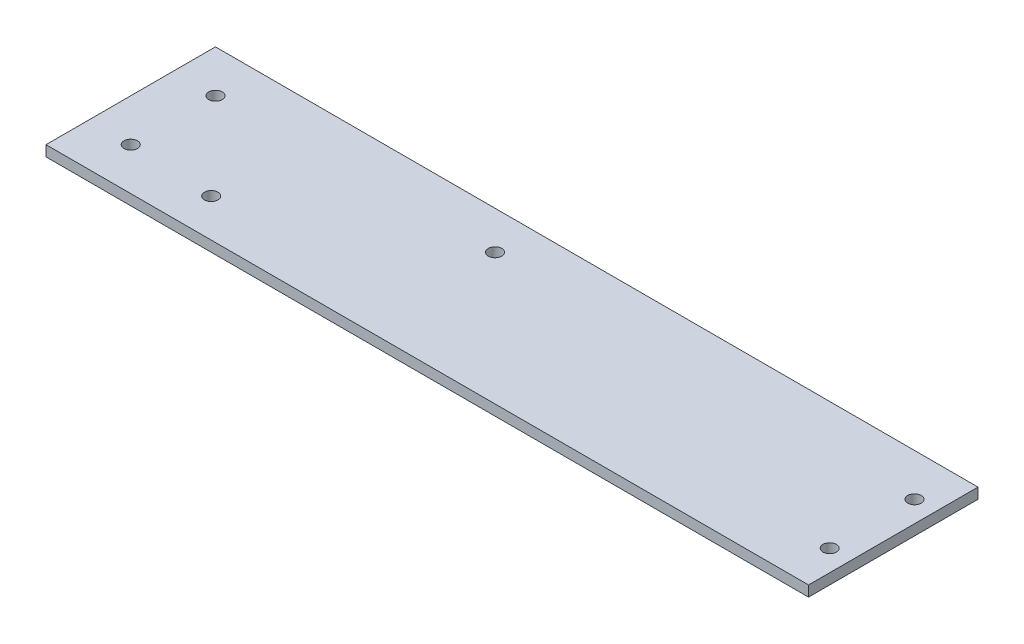
SolidWorks part; units mm, degrees
ref_plane "Front Plane" through (0, 0, 0) normal (0, 0, 1) x (1, 0, 0)
ref_plane "Top Plane" through (0, 0, 0) normal (0, 1, 0) x (1, 0, 0)
ref_plane "Right Plane" through (0, 0, 0) normal (1, 0, 0) x (0, 0, -1)
sketch "Sketch1" plane through (0, 0, 0) normal (0, 1, 0) x (1, 0, 0)
  line L1 (114.3, -25.4) -> (-114.3, -25.4)
  line L2 (114.3, -25.4) -> (114.3, 25.4)
  line L3 (114.3, 25.4) -> (-114.3, 25.4)
  line L4 (-114.3, -25.4) -> (-114.3, 25.4)
  line L5 (114.3, -25.4) -> (-114.3, 25.4) construction
  line L6 (114.3, 25.4) -> (-114.3, -25.4) construction
  point P0 (0, 0)
  dimension "D1" = 228.6
  dimension "D2" = 50.8
extrude "Boss-Extrude1" add sketch "Sketch1" along normal blind 3.175
hole_wizard "#10-32 Tapped Hole2" positions "Sketch2" profile "Sketch3" tap size "#10-32" standard "ANSI Inch" end condition through all
sketch "Sketch2" plane through (0, 3.175, 0) normal (0, 1, 0) x (1, 0, 0)
  line L0 (-101.6, 25.4) -> (-101.6, -25.4) construction
  line L1 (114.3, 25.4) -> (-114.3, 25.4) construction
  line L2 (-114.3, -25.4) -> (114.3, -25.4) construction
  line L4 (-114.3, 25.4) -> (-114.3, -25.4) construction
  line L5 (107.95, -25.4) -> (107.95, 25.4) construction
  line L7 (114.3, -25.4) -> (114.3, 25.4) construction
  point P11 (-101.6, -12.7)
  point P13 (-101.6, 12.7)
  point P23 (107.95, -12.7)
  point P25 (107.95, 12.7)
  dimension "D1" = 12.7
  dimension "D2" = 12.7
  dimension "D3" = 12.7
  dimension "D4" = 6.35
  dimension "D5" = 12.7
  dimension "D6" = 12.7
sketch "Sketch3" plane through (107.95, 3.175, -12.7) normal (1, 0, 0) x (0, 0, 1)
  line L0 (0, 0) -> (0, 3.175)
  line L1 (0, 3.175) -> (2.0193, 3.175)
  line L2 (2.0193, 3.175) -> (2.0193, 0)
  line L5 (2.0193, 0) -> (0, 0)
  line L11 (0, -6.35) -> (0, 107.95) construction
  dimension "Thread Major Dia." = 4.0386
  dimension "Thru Tap Drill Depth" = 3.175
hole_wizard "#10-32 Tapped Hole1" positions "Sketch4" profile "Sketch5" tap size "#10-32" standard "ANSI Inch" end condition through all
sketch "Sketch4" plane through (0, 3.175, 0) normal (0, 1, 0) x (1, 0, 0)
  line L0 (-114.3, 25.4) -> (-88.9, 25.4) construction
  line L1 (114.3, 25.4) -> (-114.3, 25.4) construction
  line L3 (-88.9, 25.4) -> (-88.9, -25.4) construction
  line L4 (-114.3, -25.4) -> (114.3, -25.4) construction
  line L6 (-88.9, 0) -> (-76.2, 0) construction
  line L7 (-76.2, -13.97) -> (-76.2, 0) construction
  line L9 (-76.2, 0) -> (-19.05, 0) construction
  line L10 (-19.05, 0) -> (-19.05, 13.97) construction
  point P42 (-19.05, 13.97)
  point P47 (-76.2, -13.97)
  point P63 (-77.4969, -13.97)
  dimension "D1" = 25.4
  dimension "D2" = 57.15
  dimension "D3" = 12.7
sketch "Sketch5" plane through (-76.2, 3.175, 13.97) normal (1, 0, 0) x (0, 0, 1)
  line L0 (0, 0) -> (0, 3.175)
  line L1 (0, 3.175) -> (2.0193, 3.175)
  line L2 (2.0193, 3.175) -> (2.0193, 0)
  line L5 (2.0193, 0) -> (0, 0)
  line L11 (0, -6.35) -> (0, 107.95) construction
  dimension "Thread Major Dia." = 4.0386
  dimension "Thru Tap Drill Depth" = 3.175
